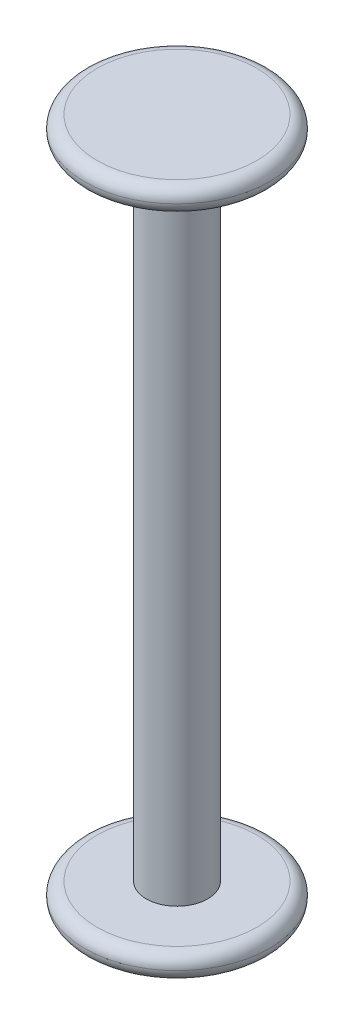
SolidWorks part; units mm, degrees
material "1060 Alloy"
ref_plane "Front Plane" through (0, 0, 0) normal (0, 0, 1) x (1, 0, 0)
ref_plane "Top Plane" through (0, 0, 0) normal (0, 1, 0) x (1, 0, 0)
ref_plane "Right Plane" through (0, 0, 0) normal (1, 0, 0) x (0, 0, -1)
sketch "Sketch1" plane through (0, 0, 0) normal (0, 1, 0) x (1, 0, 0)
  circle A0 centre (0, 0) radius 2.5
  dimension "D1" = 5
extrude "Boss-Extrude1" add sketch "Sketch1" along normal blind 26
sketch "Sketch2" plane through (0, 26, 0) normal (0, 1, 0) x (1, 0, 0)
  circle A3 centre (0, 0) radius 7.5
  point P0 (7.0303, 1.2195)
  dimension "D1" = 15
extrude "Boss-Extrude2" add sketch "Sketch2" along normal blind 2
fillet "Fillet1" radius 1 2 edges at (0, 28, 7.5) (0, 26, 7.5)
mirror "Mirror1" about plane through (0, 0, 0) normal (0, 1, 0) of bodies 102
